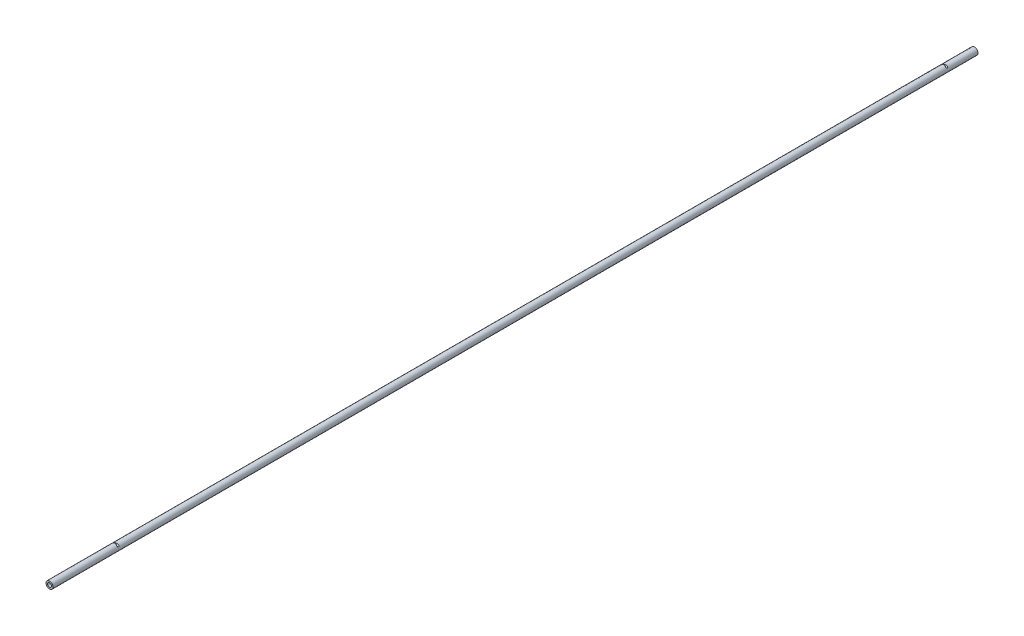
SolidWorks part; units mm, degrees
ref_plane "Front Plane" through (0, 0, 0) normal (0, 0, 1) x (1, 0, 0)
ref_plane "Top Plane" through (0, 0, 0) normal (0, 1, 0) x (1, 0, 0)
ref_plane "Right Plane" through (0, 0, 0) normal (1, 0, 0) x (0, 0, -1)
sketch "Sketch1" plane through (0, 0, 0) normal (0, 0, 1) x (1, 0, 0)
  circle A0 centre (0, 0) radius 1.98
  circle A1 centre (0, 0) radius 1.125
extrude "Extrude1" add sketch "Sketch1" along normal blind 520
sketch "Sketch2" plane through (0, 0, 0) normal (1, 0, 0) x (0, 0, -1)
  line L1 (-520, 1.98) -> (-520, -1.98) construction
  circle A0 centre (-483, 1.5) radius 0.5
  circle A1 centre (-17, 1.5) radius 0.5
  point P2 (-17, 1.5)
  dimension "D1" = 37
  dimension "D2" = 1.5
  dimension "D3" = 17
  dimension "D4" = 1.5
extrude "Extrude2" cut sketch "Sketch2" against normal through all and the other way through all
